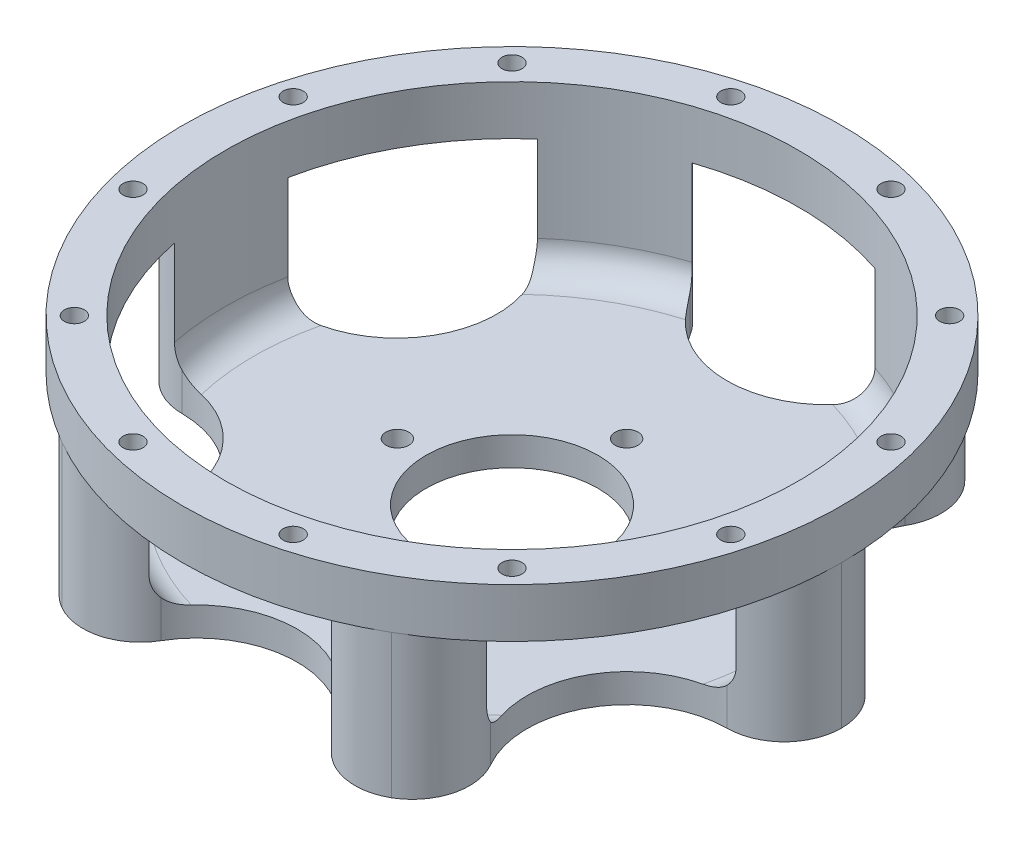
SolidWorks part; units mm, degrees
ref_plane "Front Plane" through (0, 0, 0) normal (0, 0, 1) x (1, 0, 0)
ref_plane "Top Plane" through (0, 0, 0) normal (0, 1, 0) x (1, 0, 0)
ref_plane "Right Plane" through (0, 0, 0) normal (1, 0, 0) x (0, 0, -1)
sketch "Sketch1" plane through (0, 0, 0) normal (0, 1, 0) x (1, 0, 0)
  circle A0 centre (0, 0) radius 57.5
  circle A1 centre (0, 0) radius 55 construction
  point P31 (0, 0)
  dimension "D1" = 115
  dimension "D2" = 110
extrude "Boss-Extrude1" add sketch "Sketch1" along normal blind 33.6
sketch "Sketch2" plane through (0, 33.6, 0) normal (0, 1, 0) x (1, 0, 0)
  circle A0 centre (0, 0) radius 50
  dimension "D1" = 100
extrude "Cut-Extrude1" cut sketch "Sketch2" against normal blind 28.6
sketch "Sketch7" plane through (0, 33.6, 0) normal (0, 1, 0) x (1, 0, 0)
  line L0 (-13.9762, 52.16) -> (0, 0) construction
  line L1 (0, 0) -> (13.9762, 52.16) construction
  line L2 (0, 62.0883) -> (0, -59.7095) construction
  circle A0 centre (0, 0) radius 54 construction
  circle A1 centre (-13.9762, 52.16) radius 1.75
  circle A2 centre (13.9762, 52.16) radius 1.75
  dimension "D1" = 108
  dimension "D4" = 3.5
  dimension "D2" = 15
  dimension "D3" = 15
extrude "Cut-Extrude4" cut sketch "Sketch7" against normal blind 10
fillet "Fillet2" radius 5 1 edges at (0, 5, 50)
sketch "Sketch3" plane through (0, 0, 0) normal (0, -1, 0) x (1, 0, 0)
  line L0 (0, 67.0594) -> (0, -18.0784) construction
  circle A0 centre (0, 0) radius 55 construction
  circle A1 centre (0, 55) radius 17.5
  dimension "D1" = 35
  dimension "D2" = 110
extrude "Cut-Extrude2" cut sketch "Sketch3" against normal blind 25
fillet "Fillet1" radius 10 2 edges at (-17.4985, 12.5, 54.7727) (17.4985, 12.5, 54.7727)
pattern_circular "CirPattern2" count 6 over 360 about axis through (0, 5, 0) along (0, 1, 0) of "Cut-Extrude2", "Fillet1" reverse direction yes
sketch "Sketch5" plane through (0, 0, 0) normal (0, -1, 0) x (1, 0, 0)
  circle A0 centre (0, 0) radius 20 construction
  circle A1 centre (0, 20) radius 2
  circle A2 centre (20, 0) radius 2
  circle A3 centre (0, -20) radius 2
  circle A4 centre (-20, 0) radius 2
  circle A5 centre (0, 0) radius 15
  point P14 (0, 0)
  dimension "D1" = 40
  dimension "D2" = 4
  dimension "D4" = 30
  dimension "D3" = 4
extrude "Cut-Extrude3" cut sketch "Sketch5" against normal blind 25
pattern_circular "CirPattern3" count 6 over 360 about axis through (0, 25, 0) along (0, -1, 0) of "Cut-Extrude4" reverse direction yes
